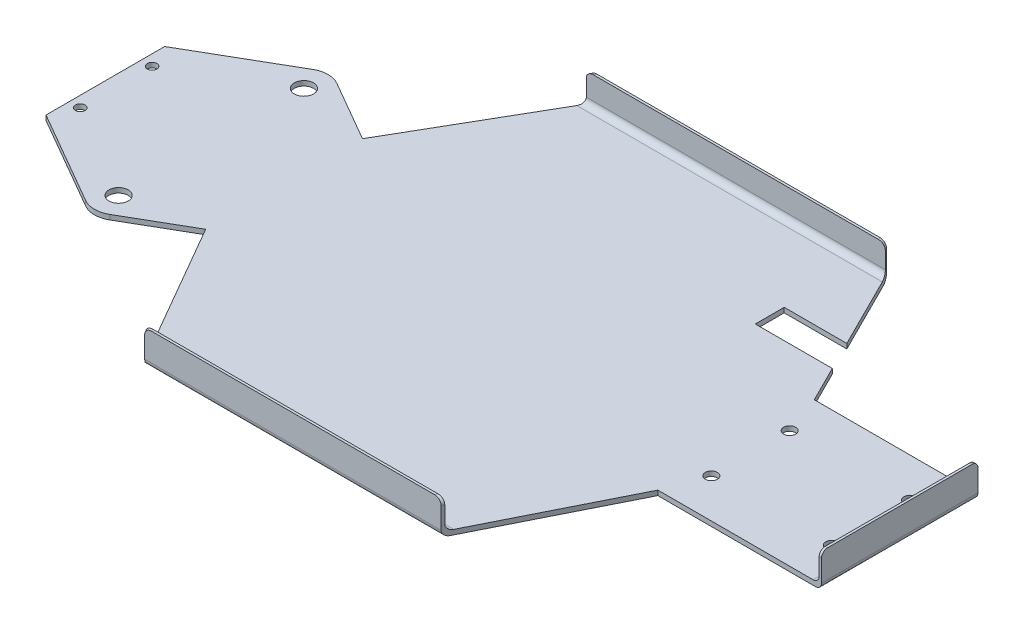
SolidWorks part; units mm, degrees
ref_plane "Front Plane" through (0, 0, 0) normal (0, 0, 1) x (1, 0, 0)
ref_plane "Top Plane" through (0, 0, 0) normal (0, 1, 0) x (1, 0, 0)
ref_plane "Right Plane" through (0, 0, 0) normal (1, 0, 0) x (0, 0, -1)
sketch "Sketch1" plane through (0, 0, 0) normal (0, 1, 0) x (1, 0, 0)
  line L0 (165, 32.5) -> (97, 32.5)
  line L1 (-89.8231, -92.5) -> (67, -92.5)
  line L3 (-56.1347, 92.5) -> (67, 92.5)
  line L4 (165, -32.5) -> (165, 32.5)
  line L5 (-165, -92.5) -> (165, 92.5) construction
  line L6 (-165, 92.5) -> (165, -92.5) construction
  line L7 (97, 32.5) -> (89.5, 47.5)
  line L8 (-187.8754, 0) -> (194.9929, 0) construction
  line L9 (165, -32.5) -> (97, -32.5)
  line L10 (97, -32.5) -> (67, -92.5)
  line L11 (165, 92.5) -> (165, 32.5) construction
  line L12 (67, 92.5) -> (165, 92.5) construction
  line L13 (67, -92.5) -> (165, -92.5) construction
  line L14 (165, -32.5) -> (165, -92.5) construction
  line L16 (103, -16.25) -> (153, -16.25) construction
  line L17 (103, -16.25) -> (103, 16.25) construction
  line L18 (103, 16.25) -> (153, 16.25) construction
  line L19 (153, -16.25) -> (153, 16.25) construction
  line L20 (103, -16.25) -> (153, 16.25) construction
  line L21 (103, 16.25) -> (153, -16.25) construction
  line L25 (-121, -38.5) -> (-89.8231, -92.5) construction
  line L26 (-56.1347, -92.5) -> (-90.7337, -32.5728)
  line L27 (-90.7337, -32.5728) -> (-116, -47.1603)
  line L28 (-121, 38.5) -> (-121, -38.5) construction
  line L29 (-126, -47.1603) -> (-165, -24.6436)
  line L30 (-90.7337, 32.5728) -> (-116, 47.1603)
  line L31 (-56.1347, 92.5) -> (-90.7337, 32.5728)
  line L32 (-165, -24.6436) -> (-165, 24.6436)
  line L33 (-89.8231, -92.5) -> (-165, -92.5) construction
  line L34 (-165, -92.5) -> (-165, 92.5) construction
  line L35 (-165, 92.5) -> (-56.1347, 92.5) construction
  line L36 (-165, 24.6436) -> (-126, 47.1603)
  line L37 (57.5, 47.5) -> (57.5, 59.5)
  line L38 (57.5, 59.5) -> (83.5, 59.5)
  line L39 (57.5, 47.5) -> (89.5, 47.5)
  line L40 (83.5, 59.5) -> (67, 92.5)
  line L41 (-121, 184.5763) -> (-121, -179.129) construction
  circle A0 centre (-121, 38.5) radius 4
  circle A1 centre (-121, -38.5) radius 4
  circle A2 centre (103, 16.25) radius 2.5
  circle A3 centre (153, 16.25) radius 2.5
  circle A4 centre (103, -16.25) radius 2.5
  circle A5 centre (153, -16.25) radius 2.5
  arc A6 (-126, -47.1603) -> (-116, -47.1603) centre (-121, -38.5) ccw
  arc A7 (-126, 47.1603) -> (-116, 47.1603) centre (-121, 38.5) cw
  circle A8 centre (-121, 0) radius 23 construction
  circle A9 centre (-160.4976, 14.92) radius 2
  circle A10 centre (-160.4976, 14.92) radius 2 construction
  circle A11 centre (-160.4976, -14.92) radius 2
  circle A12 centre (-160.4976, -14.92) radius 2 construction
  point P0 (0, 0)
  point P18 (128, 0)
  dimension "D5" = 8
  dimension "D12" = 5
  dimension "D13" = 5
  dimension "D14" = 5
  dimension "D15" = 5
  dimension "D21" = 10
  dimension "D2" = 185
  dimension "D3" = 65
  dimension "D4" = 30
  dimension "D6" = 330
  dimension "D7" = 54
  dimension "D8" = 68
  dimension "D9" = 32.5
  dimension "D10" = 50
  dimension "D11" = 12
  dimension "D16" = 15
  dimension "D19" = 60
  dimension "D20" = 29.175
  dimension "D22" = 44
  dimension "D23" = 60
  dimension "D24" = 60
  dimension "D25" = 32
  dimension "D27" = 12
extrude "Boss-Extrude1" add sketch "Sketch1" along normal blind 2 contours A7 A6 L27 L26 L1 L10 L9 L4 L0 L7 L3 L31 L30 A5 A4 A3 A2 A0 A1 region at (-1.2674, 0, 0.4579)
sketch "Sketch2" plane through (0, 2, 0) normal (0, 1, 0) x (1, 0, 0)
  line L0 (-56.1347, -92.5) -> (67, -92.5)
  line L1 (67, -92.5) -> (67.5, -91.5)
  line L2 (97, -32.5) -> (67, -92.5) construction
  line L3 (67.5, -91.5) -> (-56.712, -91.5)
  line L4 (-56.1347, -92.5) -> (-90.7337, -32.5728) construction
  line L5 (-56.712, -91.5) -> (-56.1347, -92.5)
  line L6 (-56.1347, 92.5) -> (67, 92.5)
  line L7 (67, 92.5) -> (67.5, 91.5)
  line L8 (83.5, 59.5) -> (67, 92.5) construction
  line L9 (67.5, 91.5) -> (-56.712, 91.5)
  line L10 (-56.1347, 92.5) -> (-90.7337, 32.5728) construction
  line L11 (-56.712, 91.5) -> (-56.1347, 92.5)
  line L16 (165, 32.5) -> (97, 32.5) construction
  line L17 (165, -32.5) -> (164, -32.5)
  line L18 (165, -32.5) -> (165, 32.5)
  line L19 (165, 32.5) -> (164, 32.5)
  line L20 (164, -32.5) -> (164, 32.5)
  dimension "D1" = 1
  dimension "D2" = 1
  dimension "D3" = 1
extrude "Boss-Extrude2" add sketch "Sketch2" along normal blind 12
fillet "Fillet1" radius 2.5 12 edges at (67.25, 14, 92) (-56.4234, 14, 92) (-56.4234, 14, -92) (67.25, 14, -92) (5.394, 2, 91.5) (5.4327, 0, 92.5) (5.4327, 0, -92.5) (5.394, 2, -91.5) (164.5, 14, -32.5) (164, 2, 0) (164.5, 14, 32.5) (165, 0, 0)
